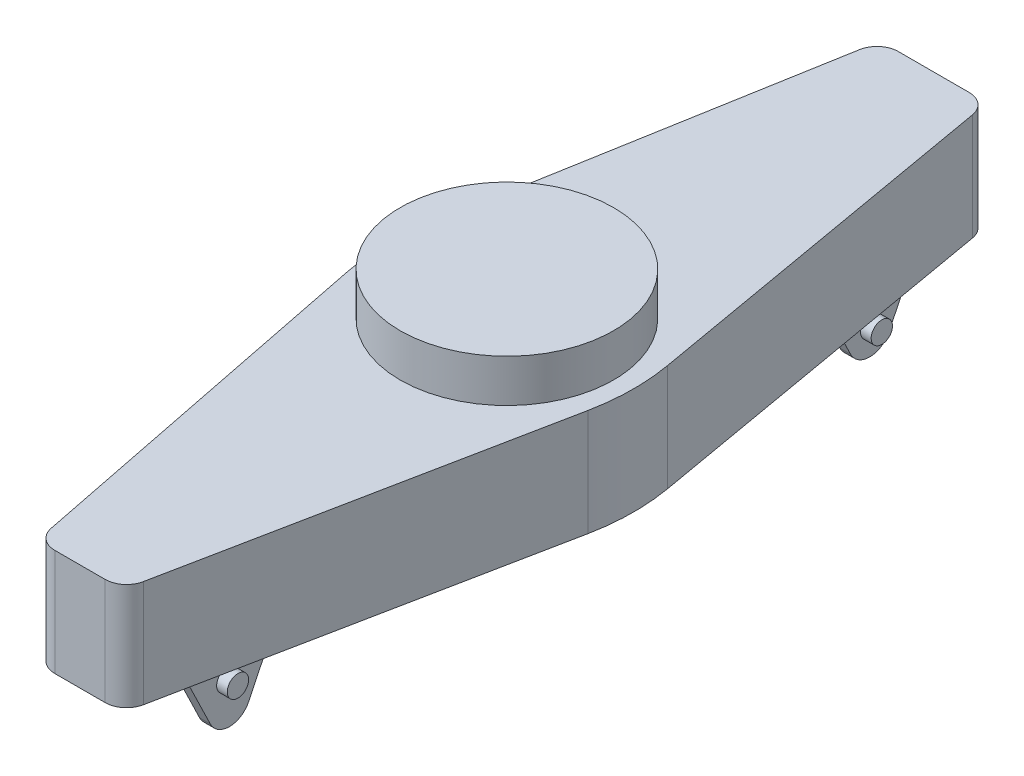
SolidWorks part; units mm, degrees
ref_plane "Front Plane" through (0, 0, 0) normal (0, 0, 1) x (1, 0, 0)
ref_plane "Top Plane" through (0, 0, 0) normal (0, 1, 0) x (1, 0, 0)
ref_plane "Right Plane" through (0, 0, 0) normal (1, 0, 0) x (0, 0, -1)
sketch "Sketch2" plane through (0, 0, 0) normal (0, 1, 0) x (1, 0, 0)
  line L0 (0, 200) -> (0, -200) construction
  line L1 (25, 200) -> (-25, 200)
  line L2 (-25, 200) -> (-60, 0)
  line L3 (-60, 0) -> (-20, -200)
  line L4 (-20, -200) -> (20, -200)
  line L5 (60, 0) -> (20, -200)
  line L6 (25, 200) -> (60, 0)
  dimension "D1" = 400
  dimension "D2" = 200
  dimension "D3" = 60
  dimension "D4" = 25
  dimension "D5" = 20
extrude "Boss-Extrude1" add sketch "Sketch2" along normal blind 25 and the other way blind 25
sketch "Sketch3" plane through (0, 0, 0) normal (0, 1, 0) x (1, 0, 0)
  circle A0 centre (0, 0) radius 50
  dimension "D2" = 100
  dimension "D1" = 0
extrude "Boss-Extrude2" add sketch "Sketch3" along normal blind 45 separate body
ref_plane "Plane1" through (15, 0, 0) normal (1, 0, 0) x (0, 0, -1)
sketch "Sketch6" plane through (15, 0, 0) normal (1, 0, 0) x (0, 0, -1)
  line L0 (128.9037, -25) -> (140.9981, -50)
  line L2 (128.9037, -25) -> (171.0963, -25)
  line L3 (159.0019, -50) -> (171.0963, -25)
  line L4 (0, -25) -> (0, 25) construction
  line L5 (-128.9037, -25) -> (-140.9981, -50)
  line L6 (-159.0019, -50) -> (-171.0963, -25)
  line L7 (-128.9037, -25) -> (-171.0963, -25)
  arc A0 (159.0019, -50) -> (140.9981, -50) centre (150, -45.6451) cw
  arc A1 (-159.0019, -50) -> (-140.9981, -50) centre (-150, -45.6451) ccw
  dimension "D4" = 10
  dimension "D5" = 0
  dimension "D6" = 25
  dimension "D8" = 150
extrude "Boss-Extrude3" add sketch "Sketch6" along normal blind 5
mirror "Mirror2" about plane through (0, 0, 0) normal (1, 0, 0) of "Boss-Extrude3"
fillet "Fillet1" radius 100 2 edges at (60, 0, 0) (-60, 0, 0)
fillet "Fillet3" radius 10 4 edges at (20, 0, 200) (-20, 0, 200) (25, 0, -200) (-25, 0, -200)
sketch "Sketch7" plane through (20, 0, 0) normal (1, 0, 0) x (0, 0, -1)
  circle A0 centre (-151.0026, -36.0612) radius 5
sketch "Sketch8" plane through (20, 0, 0) normal (1, 0, 0) x (0, 0, -1)
  circle A0 centre (150.6721, -43.3905) radius 5
extrude "Boss-Extrude4" add sketch "Sketch7" along normal blind 5 and the other way blind 45
extrude "Boss-Extrude5" add sketch "Sketch8" along normal blind 5 and the other way blind 45
